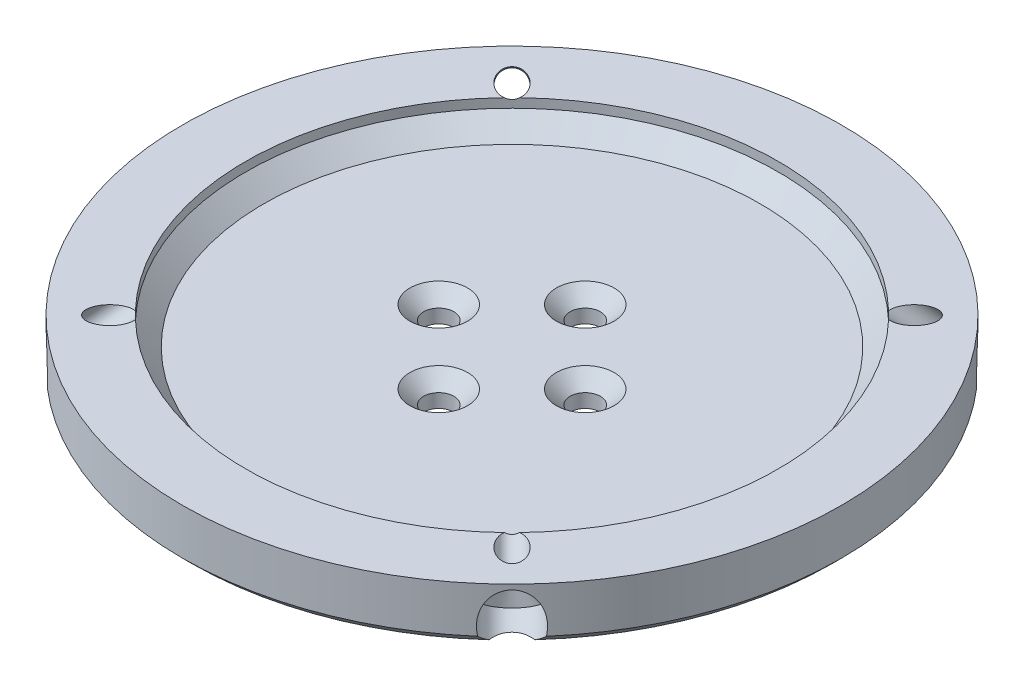
SolidWorks part; units mm, degrees
ref_plane "Front Plane" through (0, 0, 0) normal (0, 0, 1) x (1, 0, 0)
ref_plane "Top Plane" through (0, 0, 0) normal (0, 1, 0) x (1, 0, 0)
ref_plane "Right Plane" through (0, 0, 0) normal (1, 0, 0) x (0, 0, -1)
sketch "Sketch1" plane through (0, 0, 0) normal (0, 1, 0) x (1, 0, 0)
  circle A0 centre (0, 0) radius 36
  dimension "D1" = 72
extrude "Boss-Extrude1" add sketch "Sketch1" along normal mid plane 3
sketch "Sketch2" plane through (0, 1.5, 0) normal (0, 1, 0) x (1, 0, 0)
  circle A0 centre (0, 0) radius 8 construction
  circle A1 centre (0, 8) radius 1.5
  circle A2 centre (8, 0) radius 1.5
  circle A3 centre (0, -8) radius 1.5
  circle A4 centre (-8, 0) radius 1.5
  point P13 (0, 0)
  dimension "D1" = 16
  dimension "D2" = 3
  dimension "D3" = 4
hole_wizard "CSK for M3 Flat Head Machine Screw1" positions "Sketch3" profile "Sketch4" countersink size "M3" standard "ANSI Metric" end condition through all
sketch "Sketch3" plane through (0, 1.5, 0) normal (0, 1, 0) x (1, 0, 0)
  point P0 (0, 8)
  point P3 (-8, 0)
  point P6 (0, -8)
  point P9 (8, 0)
sketch "Sketch4" plane through (0, 1.5, -8) normal (1, 0, 0) x (0, 0, 1)
  line L0 (0, 0) -> (0, 3)
  line L1 (0, 3) -> (1.65, 3)
  line L2 (1.65, 3) -> (1.65, 1.5)
  line L3 (1.65, 1.5) -> (3.15, 0)
  line L5 (3.15, 0) -> (0, 0)
  line L6 (-1.65, 1.5) -> (-3.15, 0) construction
  line L11 (0, -6.35) -> (0, 107.95) construction
  dimension "Thru Hole Dia." = 3.3
  dimension "Thru Hole Depth" = 3
  dimension "Near C'Sink Dia." = 6.3
  dimension "Near C'Sink Angle" = 90
sketch "Sketch5" plane through (0, 1.5, 0) normal (0, 1, 0) x (1, 0, 0)
  circle A0 centre (0, 0) radius 29.1
  circle A1 centre (0, 0) radius 36
  circle A2 centre (0, 0) radius 36
  dimension "D2" = 58.2
  dimension "D1" = 0
extrude "Boss-Extrude2" add sketch "Sketch5" along normal blind 3
chamfer "Chamfer1" distance 1 angle 45 1 edges at (0, -1.5, 36)
ref_plane "Plane1" through (16.5389, -18.4262, -16.5389) normal (-0.5417, 0.6428, 0.5417) x (-0.7071, 0, -0.7071)
sketch "Sketch6" plane through (16.5389, -18.4262, -16.5389) normal (-0.5417, 0.6428, 0.5417) x (-0.7071, 0, -0.7071)
  circle A1 centre (0, -22.5) radius 1.4
  circle A2 centre (0, -22.5) radius 1.4
  dimension "D1" = 0
extrude "Cut-Extrude1" cut sketch "Sketch6" along normal through all
ref_plane "Plane2" through (15.4556, -17.1406, -15.4556) normal (-0.5417, 0.6428, 0.5417) x (-0.7071, 0, -0.7071)
sketch "Sketch7" plane through (16.5389, -18.4262, -16.5389) normal (-0.5417, 0.6428, 0.5417) x (-0.7071, 0, -0.7071)
  circle A1 centre (0, -22.5) radius 2.75
  circle A3 centre (0, -22.5) radius 1.4 construction
  dimension "D1" = 5.5
extrude "Cut-Extrude3" cut sketch "Sketch7" along normal blind 5.5 and the other way blind 4
ref_axis "Axis1" through (0, -2.6041, 0) along (0, 1, 0)
ref_plane "Plane3" through (0, 0, 0) normal (-0.7071, 0, -0.7071) x (0, 1, 0)
sketch "Sketch10" plane through (0, 0, 0) normal (-0.7071, 0, -0.7071) x (0, 1, 0)
  spline S0 degree 2 poles (3.9539, 36) (1.7943, 35.8671) (-0.5, 35.9021) knots 0 0 0 0.613993 0.613993 0.613993 weights 0.03325 0.034938 0.036627 construction
  spline S1 degree 2 poles (3.9539, 36) (1.7943, 35.8671) (-0.5, 35.9021) knots 0 0 0 0.613993 0.613993 0.613993 weights 0.03325 0.034938 0.036627
sketch "Sketch11" plane through (13.1419, -15.5951, -13.1419) normal (0.5417, -0.6428, -0.5417) x (0.8406, 0.4142, 0.3491)
  circle A0 centre (12.6632, -19.7004) radius 1.4 construction
  circle A1 centre (12.6632, -19.7004) radius 2.75
  circle A2 centre (12.6632, -19.7004) radius 2.75
  circle A3 centre (12.6632, -19.7004) radius 1.4
  dimension "D1" = 0
extrude "Boss-Extrude3" add sketch "Sketch11" along normal up to vertex up to point (25.4558, 3.9539, -25.4558)
hole_wizard "CSK for M2.5 Flat Head Machine Screw2" positions "Sketch12" profile "Sketch13" countersink size "M2.5" standard "ANSI Metric" end condition through all
sketch "Sketch12" plane through (13.5614, -16.0929, -13.5614) normal (0.5417, -0.6428, -0.5417) x (-0.8406, -0.4142, -0.3491)
  point P0 (-12.6632, 19.7004)
sketch "Sketch13" plane through (24.2059, 1.8473, -24.2059) normal (0.7071, 0, 0.7071) x (0.4545, 0.766, -0.4545)
  line L0 (0, 0) -> (0, 66.9719)
  line L1 (0, 66.9719) -> (1.35, 66.9719)
  line L2 (1.35, 66.9719) -> (1.35, 1.4)
  line L3 (1.35, 1.4) -> (2.75, 0)
  line L5 (2.75, 0) -> (0, 0)
  line L6 (-1.35, 1.4) -> (-2.75, 0) construction
  line L11 (0, -6.35) -> (0, 107.95) construction
  dimension "Thru Hole Dia." = 2.7
  dimension "Thru Hole Depth" = 66.9719
  dimension "Near C'Sink Dia." = 5.5
  dimension "Near C'Sink Angle" = 90
pattern_circular "CirPattern1" count 4 over 360 about axis through (0, -2.6041, 0) along (0, 1, 0) of "CSK for M2.5 Flat Head Machine Screw2", "Cut-Extrude3", "Cut-Extrude1", "Boss-Extrude3"
chamfer "Chamfer2" distance 2 angle 45 1 edges at (0, 1.5, 29.1)
